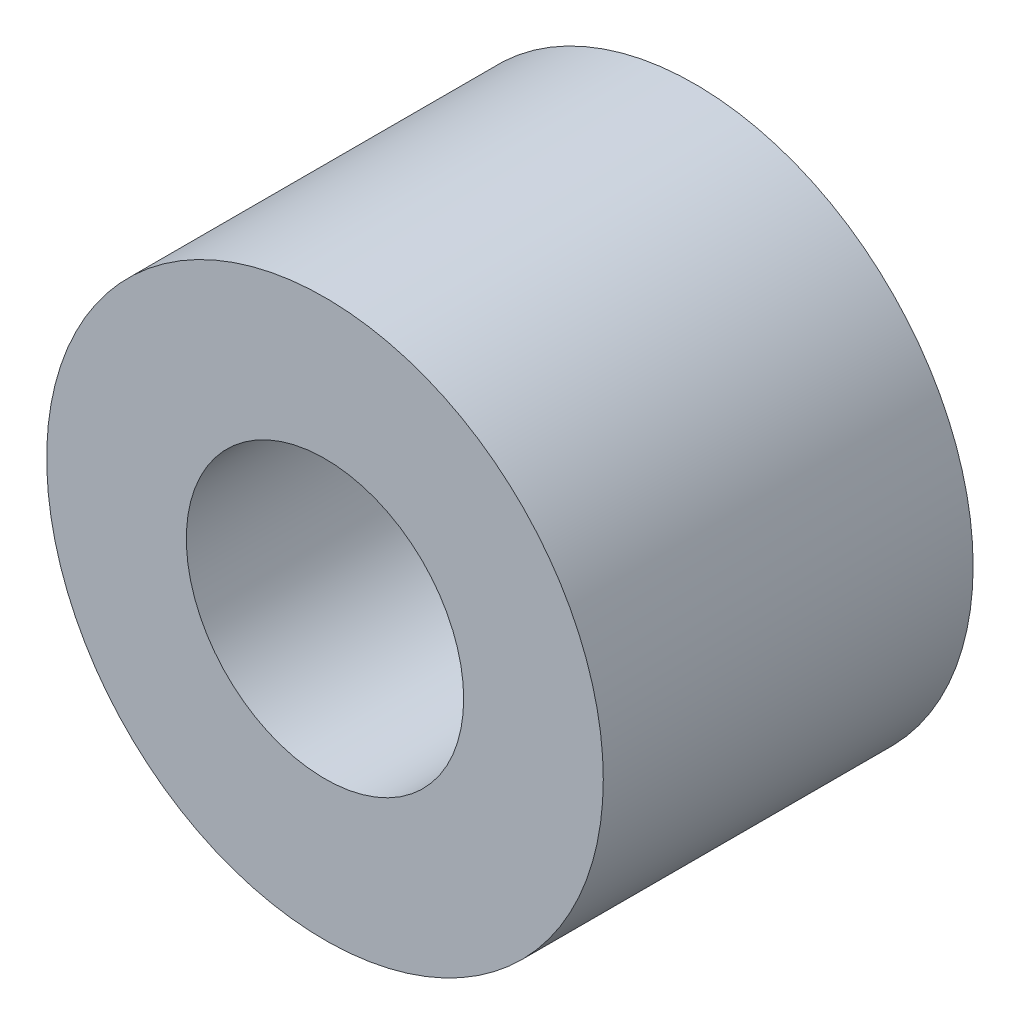
SolidWorks part; units mm, degrees
ref_plane "Front Plane" through (0, 0, 0) normal (0, 0, 1) x (1, 0, 0)
ref_plane "Top Plane" through (0, 0, 0) normal (0, 1, 0) x (1, 0, 0)
ref_plane "Right Plane" through (0, 0, 0) normal (1, 0, 0) x (0, 0, -1)
sketch "Sketch1" plane through (0, 0, 0) normal (0, 0, 1) x (1, 0, 0)
  circle A0 centre (0, 0) radius 3.01
  circle A1 centre (0, 0) radius 1.5
  dimension "ID" = 3
  dimension "OD" = 6.02
extrude "Boss-Extrude1" add sketch "Sketch1" along normal mid plane 4
sketch "Sketch2" plane through (0, 0, 0) normal (1, 0, 0) x (0, 0, -1)
  line L0 (-2, 3.01) -> (2, 3.01)
  line L1 (-2, 0) -> (2, 0) construction
  line L2 (-2, 3.01) -> (-2, -3.01) construction
  line L3 (2, -3.01) -> (2, 3.01) construction
  dimension "D1" = 6.02
  dimension "D2" = 4
ref_axis "Center Axis 1" through (0, 0, 4.4) along (0, 0, -1)
ref_plane "Contact Plane 1" through (0, 0, 2) normal (0, 0, 1) x (1, 0, 0)
ref_plane "Contact Plane 2" through (0, 0, -2) normal (0, 0, -1) x (-1, 0, 0)
equation "\"D1@Sketch2\"=\"OD@Sketch1\""
